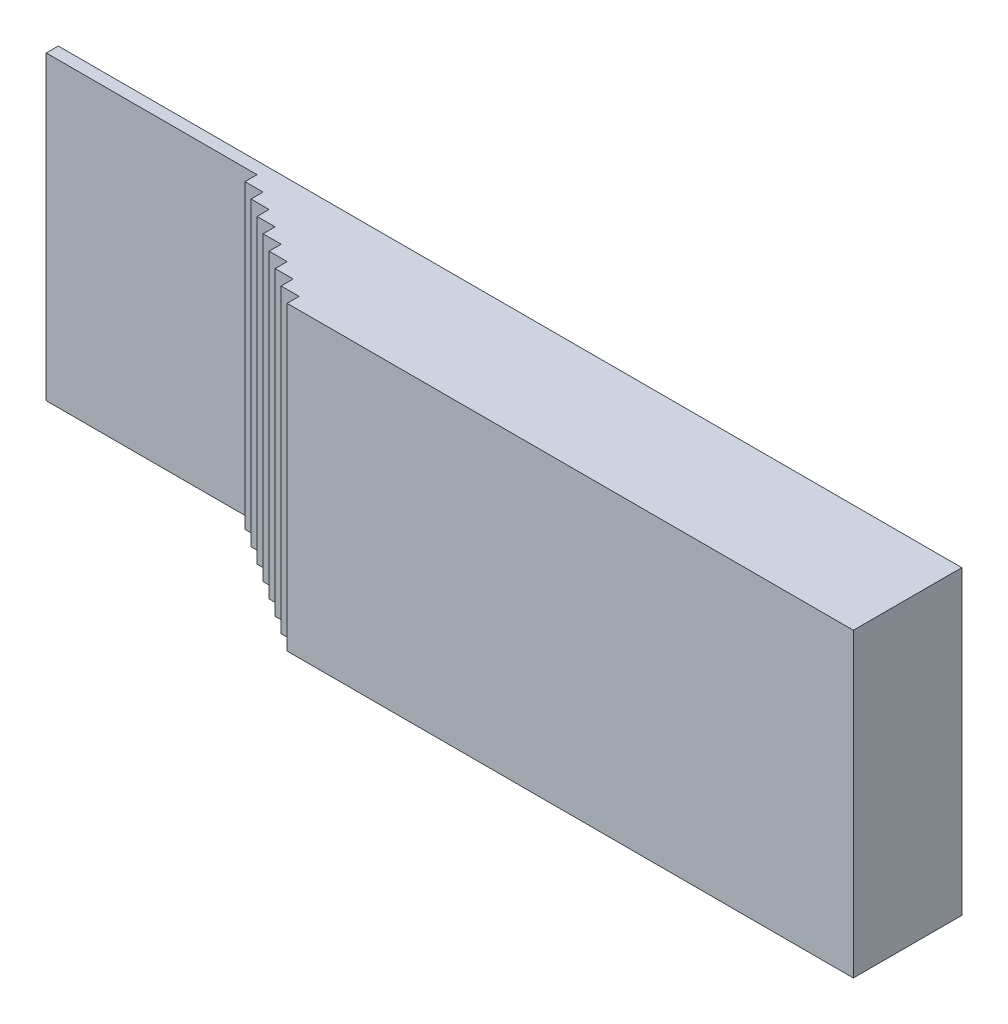
SolidWorks part; units mm, degrees
ref_plane "Front Plane" through (0, 0, 0) normal (0, 0, 1) x (1, 0, 0)
ref_plane "Top Plane" through (0, 0, 0) normal (0, 1, 0) x (1, 0, 0)
ref_plane "Right Plane" through (0, 0, 0) normal (1, 0, 0) x (0, 0, -1)
sketch "Sketch3" plane through (0, 0, 0) normal (0, 0, 1) x (1, 0, 0)
  line L1 (-2500, 2500) -> (12500, 2500)
  line L2 (-2500, 2500) -> (-2500, -2500)
  line L3 (-2500, -2500) -> (12500, -2500)
  line L4 (12500, 2500) -> (12500, -2500)
  line L5 (-2500, 2500) -> (12500, -2500) construction
  line L6 (-2500, -2500) -> (12500, 2500) construction
  point P0 (5000, 0)
  point P6 (0, 0)
  point P7 (0, 0)
  dimension "D1" = 15000
  dimension "D2" = 5000
  dimension "D3" = 5000
extrude "Boss-Extrude1" add sketch "Sketch3" along normal blind 200
sketch "Sketch4" plane through (0, 0, 200) normal (0, 0, 1) x (1, 0, 0)
  line L0 (-2500, -2500) -> (12500, -2500) construction
  line L1 (1000, -2500) -> (1300, -2500)
  line L2 (1000, -2500) -> (1000, 2500)
  line L3 (1000, 2500) -> (1300, 2500)
  line L4 (1300, -2500) -> (1300, 2500)
  line L5 (12500, 2500) -> (-2500, 2500) construction
  line L6 (1300, -2500) -> (1300, 2500)
  line L7 (1300, -2500) -> (1600, -2500)
  line L8 (1600, -2500) -> (1600, 2500)
  line L9 (1300, 2500) -> (1600, 2500)
  line L10 (1600, -2500) -> (1600, 2500)
  line L11 (1600, -2500) -> (1900, -2500)
  line L12 (1900, -2500) -> (1900, 2500)
  line L13 (1600, 2500) -> (1900, 2500)
  line L14 (1900, -2500) -> (1900, 2500)
  line L15 (1900, -2500) -> (2200, -2500)
  line L16 (2200, -2500) -> (2200, 2500)
  line L17 (1900, 2500) -> (2200, 2500)
  line L18 (2200, -2500) -> (2200, 2500)
  line L19 (2200, -2500) -> (2500, -2500)
  line L20 (2500, -2500) -> (2500, 2500)
  line L21 (2200, 2500) -> (2500, 2500)
  line L22 (2500, -2500) -> (2500, 2500)
  line L23 (2500, -2500) -> (2800, -2500)
  line L24 (2800, -2500) -> (2800, 2500)
  line L25 (2500, 2500) -> (2800, 2500)
  line L26 (2800, -2500) -> (2800, 2500)
  line L27 (2800, -2500) -> (3100, -2500)
  line L28 (3100, -2500) -> (3100, 2500)
  line L29 (2800, 2500) -> (3100, 2500)
  line L30 (3100, -2500) -> (3100, 2500)
  line L31 (3100, -2500) -> (3400, -2500)
  line L32 (3400, -2500) -> (3400, 2500)
  line L33 (3100, 2500) -> (3400, 2500)
  line M6 (12500, 2500) -> (-2500, 2500)
  line M8 (-2500, -2500) -> (12500, -2500)
  dimension "D1" = 1000
  dimension "D2" = 300
  dimension "D3" = 8
extrude "Step1" add sketch "Sketch4" along normal blind 200 contours L4 L2 M8 M6 region at (1150, 0, 200)
extrude "Step2" add sketch "Sketch4<4>" along normal blind 400 contours L8 L4 M8 M6 region at (1450, 0, 200)
sketch "Sketch4<4>" plane through (0, 0, 200) normal (0, 0, 1) x (1, 0, 0) same geometry as "Sketch4"
extrude "Step3" add sketch "Sketch4<5>" along normal blind 600 contours L12 L8 M8 M6 region at (1750, 0, 200)
sketch "Sketch4<5>" plane through (0, 0, 200) normal (0, 0, 1) x (1, 0, 0) same geometry as "Sketch4"
extrude "Step4" add sketch "Sketch4<6>" along normal blind 800 contours L16 L12 M8 M6 region at (2050, 0, 200)
sketch "Sketch4<6>" plane through (0, 0, 200) normal (0, 0, 1) x (1, 0, 0) same geometry as "Sketch4"
extrude "Boss-Extrude7" add sketch "Sketch4<7>" along normal blind 1000 contours L20 L16 M8 M6 region at (2350, 0, 200)
sketch "Sketch4<7>" plane through (0, 0, 200) normal (0, 0, 1) x (1, 0, 0) same geometry as "Sketch4"
extrude "Boss-Extrude8" add sketch "Sketch4<8>" along normal blind 1200 contours L24 L20 M8 M6 region at (2650, 0, 200)
sketch "Sketch4<8>" plane through (0, 0, 200) normal (0, 0, 1) x (1, 0, 0) same geometry as "Sketch4"
extrude "Boss-Extrude9" add sketch "Sketch4<9>" along normal blind 1400 contours L28 L24 M8 M6 region at (2950, 0, 200)
sketch "Sketch4<9>" plane through (0, 0, 200) normal (0, 0, 1) x (1, 0, 0) same geometry as "Sketch4"
extrude "Boss-Extrude10" add sketch "Sketch4<10>" along normal blind 1600 contours L32 L28 M8 M6 region at (3250, 0, 200)
sketch "Sketch4<10>" plane through (0, 0, 200) normal (0, 0, 1) x (1, 0, 0) same geometry as "Sketch4"
sketch "Sketch8" plane through (0, 0, 200) normal (0, 0, 1) x (1, 0, 0)
  line L4 (12500, 2500) -> (3400, 2500)
  line L5 (3400, 2500) -> (3400, -2500)
  line L6 (3400, -2500) -> (12500, -2500)
  line L7 (12500, -2500) -> (12500, 2500)
  line L8 (12500, 2500) -> (3400, 2500)
  line L10 (3400, -2500) -> (12500, -2500)
  line L11 (12500, -2500) -> (12500, 2500)
  line L12 (3400, 2500) -> (3400, -2500)
  dimension "D1" = 0
extrude "Boss-Extrude11" add sketch "Sketch8" along direction (0, 0, 1) on the side of the normal blind 1600
